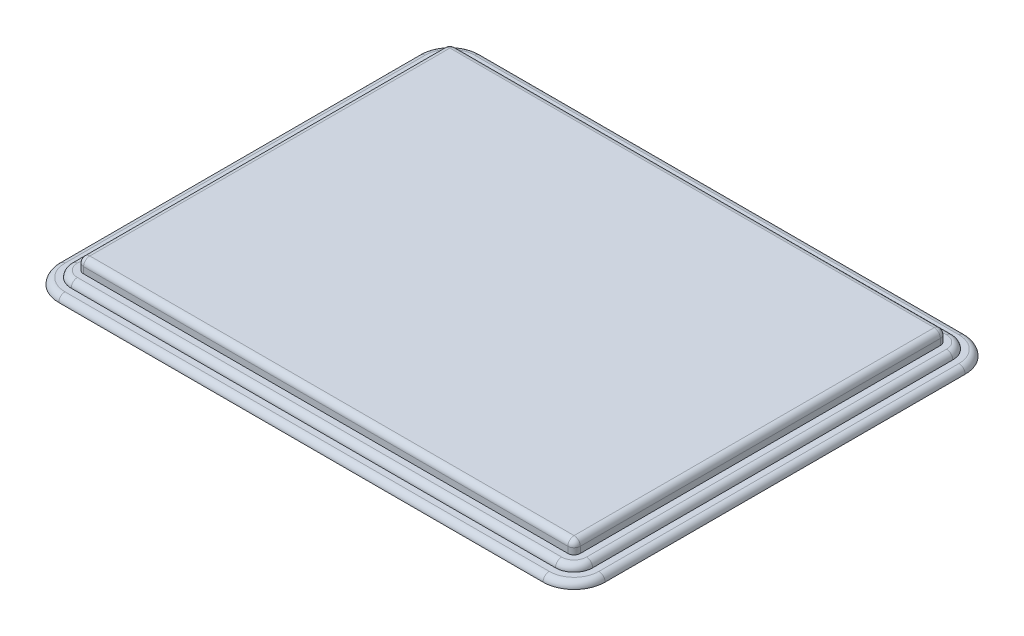
SolidWorks part; units mm, degrees
ref_plane "Front Plane" through (0, 0, 0) normal (0, 0, 1) x (1, 0, 0)
ref_plane "Top Plane" through (0, 0, 0) normal (0, 1, 0) x (1, 0, 0)
ref_plane "Right Plane" through (0, 0, 0) normal (1, 0, 0) x (0, 0, -1)
sketch "Sketch1" plane through (0, 0, 0) normal (0, 1, 0) x (1, 0, 0)
  line L2 (-1950, 1500) -> (1950, 1500)
  line L3 (-2000, 1450) -> (-2000, -1450)
  line L4 (-1950, -1500) -> (1950, -1500)
  line L5 (2000, 1450) -> (2000, -1450)
  line L6 (-2000, 1500) -> (2000, -1500) construction
  line L7 (-2000, -1500) -> (2000, 1500) construction
  arc A0 (1950, 1500) -> (2000, 1450) centre (1950, 1450) cw
  arc A1 (-2000, -1450) -> (-1950, -1500) centre (-1950, -1450) ccw
  arc A2 (-1950, 1500) -> (-2000, 1450) centre (-1950, 1450) ccw
  arc A3 (1950, -1500) -> (2000, -1450) centre (1950, -1450) ccw
  point P1 (0, 0)
  dimension "D3" = 50
  dimension "D1" = 3000
  dimension "D2" = 4000
extrude "Boss-Extrude1" add sketch "Sketch1" along normal blind 100
fillet "Fillet1" radius 50 8 edges at (2000, 100, 0) (1985.3553, 100, 1485.3553) (0, 100, 1500) (-1985.3553, 100, 1485.3553) (-2000, 100, 0) (-1985.3553, 100, -1485.3553) (0, 100, -1500) (1985.3553, 100, -1485.3553)
sketch "Sketch2" plane through (0, 0, 0) normal (0, -1, 0) x (1, 0, 0)
  line L0 (-2100, 1450) -> (-2100, -1450)
  line L1 (-1950, -1600) -> (1950, -1600)
  line L2 (2100, -1450) -> (2100, 1450)
  line L3 (1950, 1600) -> (-1950, 1600)
  line L4 (2000, -1450) -> (2000, 1450)
  line L5 (1950, 1500) -> (-1950, 1500)
  line L6 (-2000, 1450) -> (-2000, -1450)
  line L7 (-1950, -1500) -> (1950, -1500)
  line L8 (2000, -1450) -> (2000, 1450)
  line L9 (1950, 1500) -> (-1950, 1500)
  line L10 (-2000, 1450) -> (-2000, -1450)
  line L11 (-1950, -1500) -> (1950, -1500)
  arc A0 (-2100, -1450) -> (-1950, -1600) centre (-1950, -1450) ccw
  arc A1 (1950, -1600) -> (2100, -1450) centre (1950, -1450) ccw
  arc A2 (2100, 1450) -> (1950, 1600) centre (1950, 1450) ccw
  arc A3 (-1950, 1600) -> (-2100, 1450) centre (-1950, 1450) ccw
  arc A4 (1950, -1500) -> (2000, -1450) centre (1950, -1450) ccw
  arc A5 (2000, 1450) -> (1950, 1500) centre (1950, 1450) ccw
  arc A6 (-1950, 1500) -> (-2000, 1450) centre (-1950, 1450) ccw
  arc A7 (-2000, -1450) -> (-1950, -1500) centre (-1950, -1450) ccw
  arc A8 (1950, -1500) -> (2000, -1450) centre (1950, -1450) ccw
  arc A9 (2000, 1450) -> (1950, 1500) centre (1950, 1450) ccw
  arc A10 (-1950, 1500) -> (-2000, 1450) centre (-1950, 1450) ccw
  arc A11 (-2000, -1450) -> (-1950, -1500) centre (-1950, -1450) ccw
  arc M9 (1950, -1500) -> (2000, -1450) centre (1950, -1450) ccw
  line M10 (2000, -1450) -> (2000, 1450)
  arc M11 (2000, 1450) -> (1950, 1500) centre (1950, 1450) ccw
  line M12 (1950, 1500) -> (-1950, 1500)
  arc M13 (-1950, 1500) -> (-2000, 1450) centre (-1950, 1450) ccw
  line M14 (-2000, 1450) -> (-2000, -1450)
  arc M15 (-2000, -1450) -> (-1950, -1500) centre (-1950, -1450) ccw
  line M16 (-1950, -1500) -> (1950, -1500)
  dimension "D1" = 0
  dimension "D2" = 100
extrude "Boss-Extrude2" add sketch "Sketch2" along normal blind 50 contours M16 M9 M10 M11 M12 M13 M14 M15 | L3 A3 L0 A0 L1 A1 L2 A2 M9 M16 M15 M14 M13 M12 M11 M10 region at (-2018.7297, 0, 1518.7297) region at (0, 0, 0)
sketch "Sketch3" plane through (0, -50, 0) normal (0, -1, 0) x (1, 0, 0)
  line L0 (-2200, 1450) -> (-2200, -1450)
  line L1 (-1950, -1700) -> (1950, -1700)
  line L2 (2200, -1450) -> (2200, 1450)
  line L3 (1950, 1700) -> (-1950, 1700)
  line L4 (1950, 1600) -> (-1950, 1600)
  line L5 (-2100, 1450) -> (-2100, -1450)
  line L6 (-1950, -1600) -> (1950, -1600)
  line L7 (2100, -1450) -> (2100, 1450)
  line L8 (1950, 1600) -> (-1950, 1600)
  line L9 (-2100, 1450) -> (-2100, -1450)
  line L10 (-1950, -1600) -> (1950, -1600)
  line L11 (2100, -1450) -> (2100, 1450)
  arc A0 (-2200, -1450) -> (-1950, -1700) centre (-1950, -1450) ccw
  arc A1 (1950, -1700) -> (2200, -1450) centre (1950, -1450) ccw
  arc A2 (2200, 1450) -> (1950, 1700) centre (1950, 1450) ccw
  arc A3 (-1950, 1700) -> (-2200, 1450) centre (-1950, 1450) ccw
  arc A4 (-1950, 1600) -> (-2100, 1450) centre (-1950, 1450) ccw
  arc A5 (-2100, -1450) -> (-1950, -1600) centre (-1950, -1450) ccw
  arc A6 (1950, -1600) -> (2100, -1450) centre (1950, -1450) ccw
  arc A7 (2100, 1450) -> (1950, 1600) centre (1950, 1450) ccw
  arc A8 (-1950, 1600) -> (-2100, 1450) centre (-1950, 1450) ccw
  arc A9 (-2100, -1450) -> (-1950, -1600) centre (-1950, -1450) ccw
  arc A10 (1950, -1600) -> (2100, -1450) centre (1950, -1450) ccw
  arc A11 (2100, 1450) -> (1950, 1600) centre (1950, 1450) ccw
  line M9 (1950, 1600) -> (-1950, 1600)
  arc M10 (-1950, 1600) -> (-2100, 1450) centre (-1950, 1450) ccw
  line M11 (-2100, 1450) -> (-2100, -1450)
  arc M12 (-2100, -1450) -> (-1950, -1600) centre (-1950, -1450) ccw
  line M13 (-1950, -1600) -> (1950, -1600)
  arc M14 (1950, -1600) -> (2100, -1450) centre (1950, -1450) ccw
  line M15 (2100, -1450) -> (2100, 1450)
  arc M16 (2100, 1450) -> (1950, 1600) centre (1950, 1450) ccw
  dimension "D1" = 0
  dimension "D2" = 100
extrude "Boss-Extrude3" add sketch "Sketch3" along normal blind 50 contours M16 M9 M10 M11 M12 M13 M14 M15 | L3 A3 L0 A0 L1 A1 L2 A2 M9 M16 M15 M14 M13 M12 M11 M10 region at (-2087.4575, -50, 1587.4575) region at (0, -50, 0)
fillet "Fillet2" radius 50 16 edges at (2126.7767, -50, -1626.7767) (0, -50, -1700) (-2126.7767, -50, -1626.7767) (-2200, -50, 0) (-2126.7767, -50, 1626.7767) (0, -50, 1700) (2126.7767, -50, 1626.7767) (2056.066, 0, -1556.066) (0, 0, -1600) (-2056.066, 0, -1556.066) (-2100, 0, 0) (-2056.066, 0, 1556.066) (0, 0, 1600) (2056.066, 0, 1556.066) (2200, -50, 0) (2100, 0, 0)
